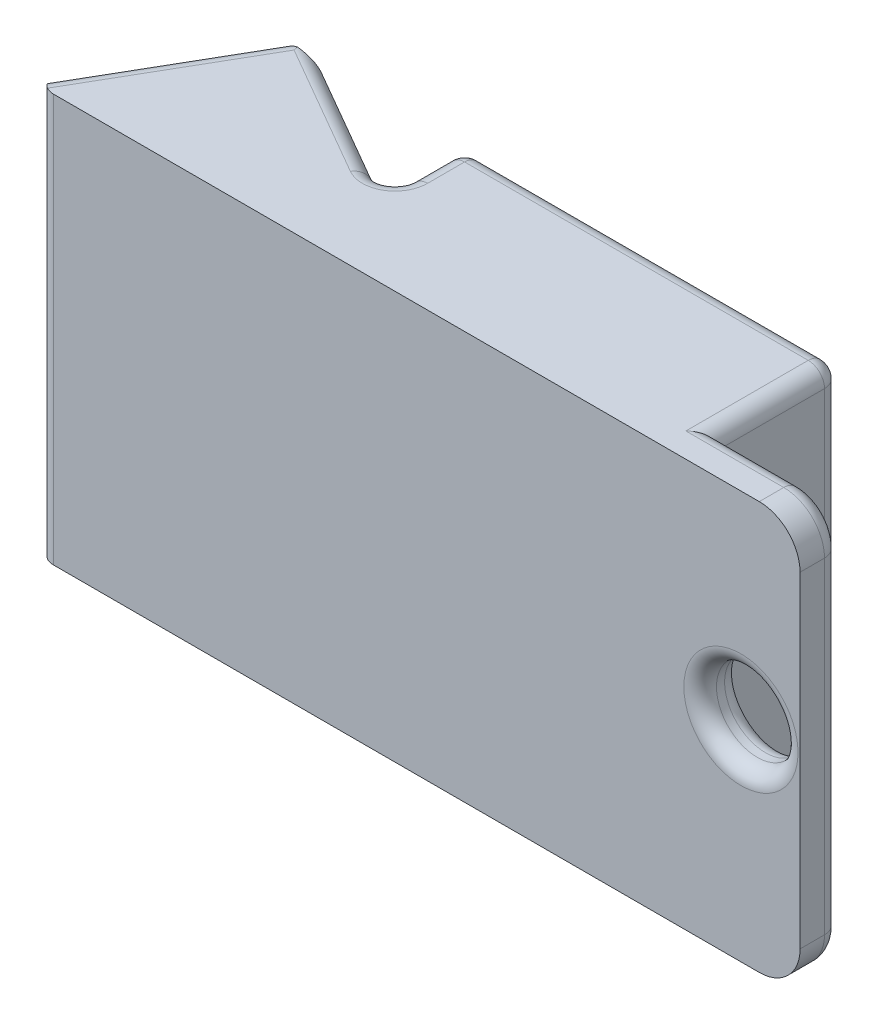
SolidWorks part; units mm, degrees
ref_plane "Front Plane" through (0, 0, 0) normal (0, 0, 1) x (1, 0, 0)
ref_plane "Top Plane" through (0, 0, 0) normal (0, 1, 0) x (1, 0, 0)
ref_plane "Right Plane" through (0, 0, 0) normal (1, 0, 0) x (0, 0, -1)
sketch "Sketch2" plane through (0, 0, 0) normal (0, 1, 0) x (1, 0, 0)
  line L1 (-32.7044, 17.6939) -> (47.2956, 17.6939)
  line L2 (-32.7044, 17.6939) -> (-32.7044, -2.3061)
  line L3 (-32.7044, -2.3061) -> (47.2956, -2.3061)
  line L4 (47.2956, 17.6939) -> (47.2956, -2.3061)
  dimension "D1" = 80
  dimension "D2" = 20
extrude "Boss-Extrude1" add sketch "Sketch2" along normal blind 50
sketch "Sketch3" plane through (0, 50, 0) normal (0, 1, 0) x (1, 0, 0)
  line L0 (-32.7044, -2.3061) -> (-21.1574, 17.6939)
  line L1 (-21.1574, 17.6939) -> (-16.1574, 17.6939)
  line L2 (-16.1574, 17.6939) -> (1.1631, 7.6939)
  line L3 (1.1631, 7.6939) -> (1.1631, 17.6939)
  line L4 (-32.7044, 17.6939) -> (-32.7044, -2.3061)
  line L5 (-32.7044, -2.3061) -> (47.2956, -2.3061)
  line L6 (47.2956, -2.3061) -> (47.2956, 17.6939)
  line L7 (47.2956, 17.6939) -> (-32.7044, 17.6939)
  line L8 (-32.7044, 17.6939) -> (-32.7044, -2.3061)
  line L9 (-32.7044, -2.3061) -> (47.2956, -2.3061)
  line L10 (47.2956, -2.3061) -> (47.2956, 17.6939)
  line L11 (47.2956, 17.6939) -> (-32.7044, 17.6939)
  line M5 (-32.7044, 17.6939) -> (-32.7044, -2.3061)
  line M8 (47.2956, 17.6939) -> (-32.7044, 17.6939)
  dimension "D2" = 30
  dimension "D3" = 5
  dimension "D4" = 30
  dimension "D5" = 20
  dimension "D1" = 0
extrude "Cut-Extrude1" cut sketch "Sketch3" against normal blind 50 contours L0 M5 M8 | L2 L3 M8 region at (-28.8554, 50, -11.0273) region at (-4.6104, 50, -14.3606)
sketch "Sketch5" plane through (0, 0, 2.3061) normal (0, 0, 1) x (1, 0, 0)
  line L0 (-32.7044, 50) -> (47.2956, 50) construction
  line L1 (47.2956, 50) -> (57.2956, 50)
  line L2 (47.2956, 50) -> (47.2956, 0)
  line L3 (47.2956, 0) -> (57.2956, 0)
  line L4 (62.2956, 45) -> (62.2956, 5)
  circle A0 centre (55.0489, 25.7156) radius 5
  arc A1 (57.2956, 0) -> (62.2956, 5) centre (57.2956, 5) ccw
  arc A2 (57.2956, 50) -> (62.2956, 45) centre (57.2956, 45) cw
  dimension "D1" = 5
  dimension "D2" = 10
  dimension "D4" = 10
  dimension "D3" = 40
extrude "Boss-Extrude2" add sketch "Sketch5" against normal blind 5
fillet "Fillet1" radius 2 22 edges at (1.1631, 0, -12.6939) (1.1631, 50, -12.6939) (52.2956, 0, -2.6939) (60.8311, 1.4645, -2.6939) (62.2956, 25, -2.6939) (60.8311, 48.5355, -2.6939) (47.2956, 25, -17.6939) (24.2294, 50, -17.6939) (1.1631, 25, -17.6939) (24.2294, 0, -17.6939) (60.0489, 25.7156, 2.3061) (60.0489, 25.7156, -2.6939) (52.2956, 50, -2.6939) (47.2956, 0, -10.1939) (47.2956, 50, -10.1939) (1.1631, 25, -7.6939) (-7.4971, 0, -12.6939) (-7.4971, 50, -12.6939) (-16.1574, 25, -17.6939) (-32.7044, 25, 2.3061) (-26.9309, 0, -7.6939) (-26.9309, 50, -7.6939)
sketch "Sketch6" plane through (0, 0, 2.3061) normal (0, 0, 1) x (1, 0, 0)
  text T0 "Ayush Patra"
